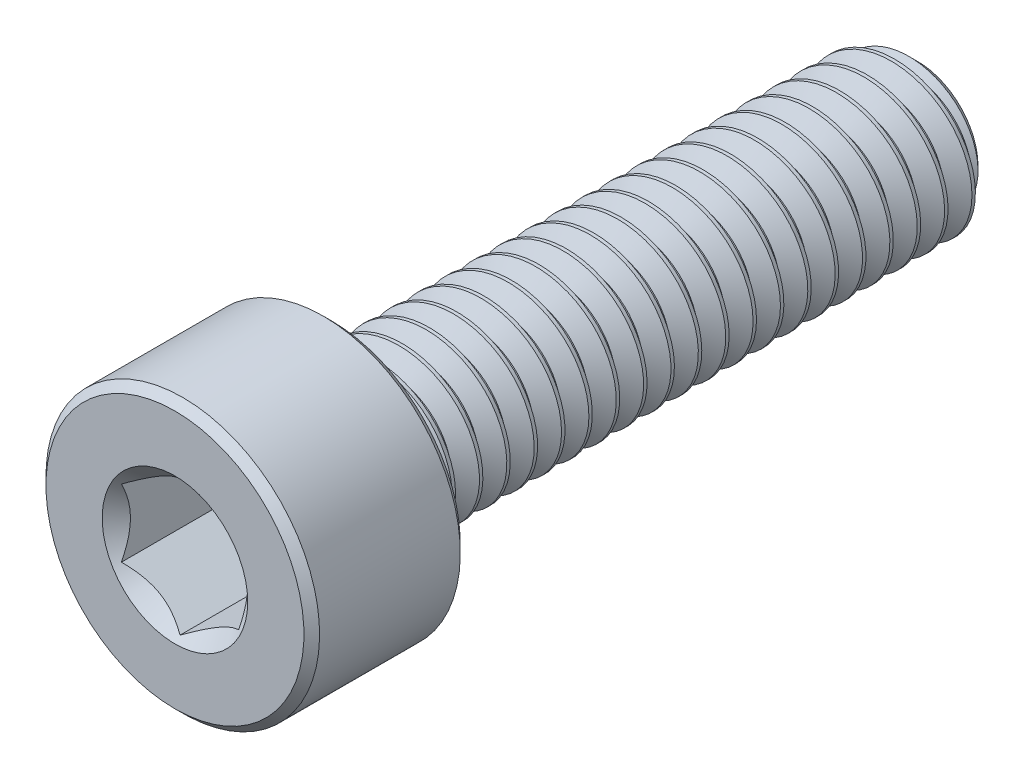
SolidWorks part; units mm, degrees
ref_plane "Front Plane" through (0, 0, 0) normal (0, 0, 1) x (1, 0, 0)
ref_plane "Top Plane" through (0, 0, 0) normal (0, 1, 0) x (1, 0, 0)
ref_plane "Right Plane" through (0, 0, 0) normal (1, 0, 0) x (0, 0, -1)
sketch "Sketch1" plane through (0, 0, 0) normal (1, 0, 0) x (0, 0, -1)
  line L0 (-9.5, 0) -> (9.5, 0) construction
  line L1 (9.5, 0) -> (9.5, 1.5453) construction
  line L2 (9.5, 1.5453) -> (9.0453, 2) construction
  line L3 (9.0453, 2) -> (8.975, 2) construction
  line L4 (8.975, 2) -> (-5.5, 2) construction
  line L5 (-5.5, 2) -> (-5.5, 3.5) construction
  line L6 (-5.5, 3.5) -> (-9.5, 3.5) construction
  line L7 (-9.5, 3.5) -> (-9.5, 0) construction
  line L8 (9.5, 1.5453) -> (9.5, 2) construction
  line L9 (9.4562, 2.0758) -> (9.8062, 1.4696) construction
  line L10 (9.8062, 1.4696) -> (10.1562, 2.0758) construction
  line L11 (10.1562, 2.0758) -> (9.4562, 2.0758) construction
  line L12 (9.8062, 2.0758) -> (9.8062, 2) construction
  line L13 (9.8062, 1.4696) -> (9.8062, 1.5453) construction
  line L14 (9.7625, 1.5453) -> (9.85, 1.5453) construction
  line L15 (9.5, 2) -> (10.1125, 2) construction
  line L16 (9.4781, 2.0379) -> (10.1344, 2.0379) construction
  line L17 (9.5, 0) -> (9.5, -2) construction
  line L18 (-5.7, 3.5) -> (-5.5, 3.3) construction
  line L19 (-9.3, 3.5) -> (-9.5, 3.3) construction
  line L20 (-5.5, 2) -> (-5.5, 0) construction
  line L21 (-5.5, 1) -> (-0.5, 1) construction
  line L22 (-0.5, 1) -> (4.5, 1) construction
  line L23 (4.5, 1) -> (9.5, 1) construction
  line L24 (-0.5, 1) -> (-0.5, 2) construction
  line L25 (-0.5, 2) -> (-0.5, 3.5) construction
  line L26 (4.5, 1) -> (4.5, 3.5) construction
  point P0 (-9.5, 1.5)
  point P3 (7.75, 2)
  point P4 (0, 0)
  point P18 (4.5, 2)
  point P22 (9.8062, 1.5453)
  point P24 (8.975, 2)
  point P25 (9.8062, 2)
  point P28 (9.8062, 2.0379)
  point P29 (7.75, -2)
  point P30 (-0.5, 2)
  point P31 (-7.5, 3.5)
  point P37 (-6.2, 3.5)
  point P38 (-9.2, 3.5)
  point P45 (-0.5, 1)
  point P46 (4.5, 1)
  dimension "D2" = 0.0875
  dimension "D7" = 0.2
  dimension "D8" = 0.2
  dimension "D9" = 0.2
  dimension "D10" = 0.1
  dimension "D11" = 0.5
  dimension "Drive Size" = 3
  dimension "Head Diameter" = 7
  dimension "Head Height" = 4
  dimension "Thread Pitch" = 0.7
  dimension "Thread Dia" = 4
  dimension "Length" = 15
  dimension "D12" = 0.525
  dimension "D4" = 1.75
  dimension "D3" = 45
sketch "Sketch2" plane through (0, 0, 0) normal (1, 0, 0) x (0, 0, -1)
  line L0 (-9.5, 0) -> (-9.5, 3.3)
  line L1 (-9.3, 3.5) -> (-5.7, 3.5)
  line L2 (-5.5, 3.3) -> (-5.5, 2.2)
  line L4 (9.0453, 2) -> (9.5, 1.5453)
  line L5 (9.5, 1.5453) -> (9.5, 0)
  line L6 (-5.5, 3.5) -> (-9.5, 3.5) construction
  line L7 (9.5, 0) -> (-9.5, 0)
  line L8 (-9.3, 3.5) -> (-9.5, 3.3) construction
  line L10 (-9.3, 3.5) -> (-9.5, 3.3)
  line L14 (-5.7, 3.5) -> (-5.5, 3.3) construction
  line L16 (-5.7, 3.5) -> (-5.5, 3.3)
  line L17 (-5.5, 2) -> (-5.5, 3.5) construction
  line L19 (-5.3, 2) -> (9.0453, 2)
  line L20 (8.975, 2) -> (-5.5, 2) construction
  arc A1 (-5.5, 2.2) -> (-5.3, 2) centre (-5.3, 2.2) ccw
  dimension "D3" = 0.2
revolve "Revolve1" add sketch "Sketch2" angle 360 about L7
sketch "Sketch3" plane through (0, 0, 9.5) normal (0, 0, 1) x (1, 0, 0)
  line L1 (1.5, -0.866) -> (1.5, 0.866)
  line L2 (1.5, 0.866) -> (0, 1.7321)
  line L3 (0, 1.7321) -> (-1.5, 0.866)
  line L4 (-1.5, 0.866) -> (-1.5, -0.866)
  line L5 (-1.5, -0.866) -> (0, -1.7321)
  line L6 (0, -1.7321) -> (1.5, -0.866)
  circle A0 centre (0, 0) radius 1.5 construction
  circle A1 centre (0, 0) radius 3.5 construction
  circle A2 centre (0, 0) radius 3.5 construction
  circle A3 centre (0, 0) radius 1.7321 construction
  point P13 (0, 0)
  dimension "D1" = 3.4641
extrude "Cut-Extrude1" cut sketch "Sketch3" against normal offset from surface (3 mm away) 1 up to face at (0, 3.3, 5.5)
sketch "Sketch4" plane through (0, 0, 9.5) normal (0, 0, 1) x (1, 0, 0)
  circle A0 centre (0, 0) radius 1.862
  dimension "D1" = 3.7239
extrude "Cut-Extrude2" cut sketch "Sketch4" against normal up to vertex (2 mm away) draft 45 up to point (0, 3.5, 7.5)
sketch "Sketch11" plane through (0, 0, 0) normal (1, 0, 0) x (0, 0, -1)
  line L0 (-9.5, 0) -> (9.5, 0) construction
  line L1 (-9.5, 0) -> (9.5, 0) construction
  line L2 (-2.6875, 0) -> (-2.6875, 2) construction
  line L3 (8.975, 2) -> (-5.5, 2) construction
  line L4 (6.6875, 0) -> (6.6875, 2) construction
  line L6 (9.5, 1.5453) -> (9.5, 2) construction
  point P2 (-2.6875, 0)
  point P3 (6.6875, 0)
  dimension "D1" = 2.8125
  dimension "D2" = 2.8125
sketch "Sketch6" plane through (0, 0, -9.5) normal (0, 0, -1) x (-1, 0, 0)
  circle A0 centre (0, 0) radius 2
curve "Helix/Spiral1" pitch 0.7 height 15.7 turns 22.4286
sketch "Sketch10" plane through (0, 0, 0) normal (1, 0, 0) x (0, 0, -1)
  line L0 (-5.3, -3.5) -> (-5.3, 3.5)
  line L5 (-9.5, 0) -> (9.5, 0) construction
  line L6 (-5.3, 2) -> (-5.3, -2) construction
  point P3 (-5.3, 0)
split "Split1" trim tools "Sketch10" bodies to split 106 resulting bodies 114 115
sketch "Sketch7" plane through (0, 0, 0) normal (1, 0, 0) x (0, 0, -1)
  line L0 (9.4781, 2.0379) -> (10.1344, 2.0379)
  line L1 (10.1344, 2.0379) -> (9.85, 1.5453)
  line L2 (9.85, 1.5453) -> (9.7625, 1.5453)
  line L3 (9.7625, 1.5453) -> (9.4781, 2.0379)
sweep "Cut-Sweep1" cut profiles "Sketch7" path "Helix/Spiral1"
sketch "Sketch8" plane through (0, 0, 0) normal (1, 0, 0) x (0, 0, -1)
  line L0 (-5.5, 0) -> (-5.5, 2)
  line L1 (-5.3, -2) -> (-5.3, 2) construction
  line L2 (-5.5, 2) -> (-5.3, 2)
  line L4 (-5.3, 2) -> (-4.1453, 0)
  line L5 (-4.1453, 0) -> (-5.5, 0)
  line L6 (8.975, 2) -> (-5.5, 2) construction
  line L7 (-9.5, 0) -> (9.5, 0) construction
  dimension "D1" = 60
revolve "Revolve2" add sketch "Sketch8" angle 360 about L5
equation "\"D2@Sketch1\" = \"Thread Pitch@Sketch1\" / 8"
equation "\"D4@Helix/Spiral1\" = \"Thread Pitch@Sketch1\""
equation "\"D7@Sketch1\" = \"Head Height@Sketch1\" * .05"
equation "\"D8@Sketch1\"=\"D7@Sketch1\""
equation "\"D9@Sketch1\"=\"D7@Sketch1\""
equation "\"D10@Sketch1\"=\"D7@Sketch1\"/2"
equation "\"D11@Sketch1\"=\"D10@Sketch1\"*5"
equation "\"D4@Sketch1\"=\"Thread Pitch@Sketch1\"*2.5"
equation "\"D12@Sketch1\"=\"Thread Pitch@Sketch1\"*.75"
equation "\"D3@Helix/Spiral1\"=\"Length@Sketch1\"+\"Thread Pitch@Sketch1\""
equation "\"D3@Sketch2\"=\"Thread Dia@Sketch1\"*0.05"
equation "\"D1@Sketch11\"=\"Length@Sketch1\"*0.1875"
equation "\"D2@Sketch11\"=\"D1@Sketch11\""
equation "\"D1@Sketch4\"=\"D1@Sketch3\"*1.075"
